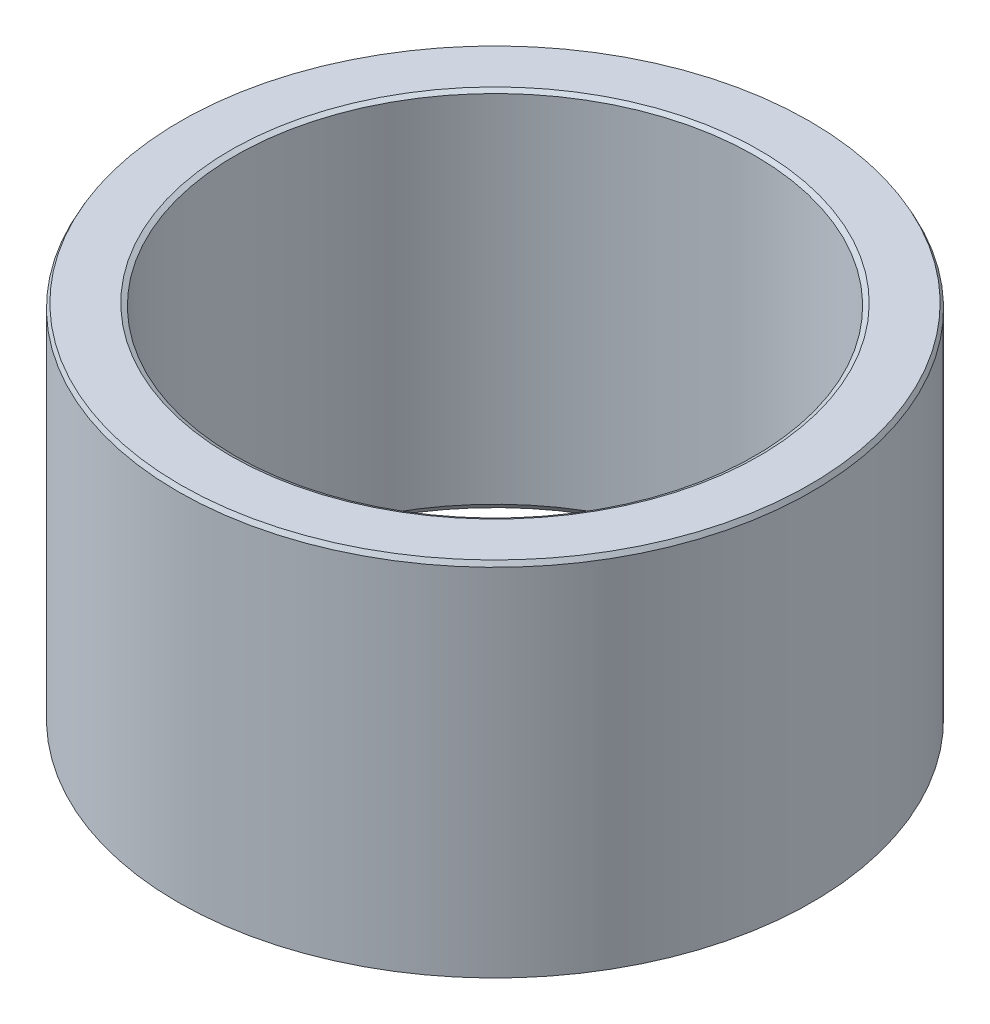
SolidWorks part; units mm, degrees
ref_plane "Front Plane" through (0, 0, 0) normal (0, 0, 1) x (1, 0, 0)
ref_plane "Top Plane" through (0, 0, 0) normal (0, 1, 0) x (1, 0, 0)
ref_plane "Right Plane" through (0, 0, 0) normal (1, 0, 0) x (0, 0, -1)
sketch "Sketch1" plane through (0, 0, 0) normal (0, 1, 0) x (1, 0, 0)
  circle A0 centre (0, 0) radius 35
  dimension "SLEEVE_OD" = 70
extrude "Boss-Extrude1" add sketch "Sketch1" along normal blind 40.0247
sketch "Sketch2" plane through (0, 0, 0) normal (0, 1, 0) x (1, 0, 0)
  circle A0 centre (0, 0) radius 28.6856
  dimension "BORE_D" = 57.3711
extrude "Cut-Extrude1" cut sketch "Sketch2" along normal through all
chamfer "Chamfer1" distance 0.5128 angle 27.502 4 edges at (0, 40.0247, 28.6856) (0, 0, 28.6856) (0, 0, 35) (0, 40.0247, 35) first distance on face at (0, 40.0247, 28.6856) first distance on face at (0, 0, 28.6856) first distance on face at (0, 40.0247, 35)
